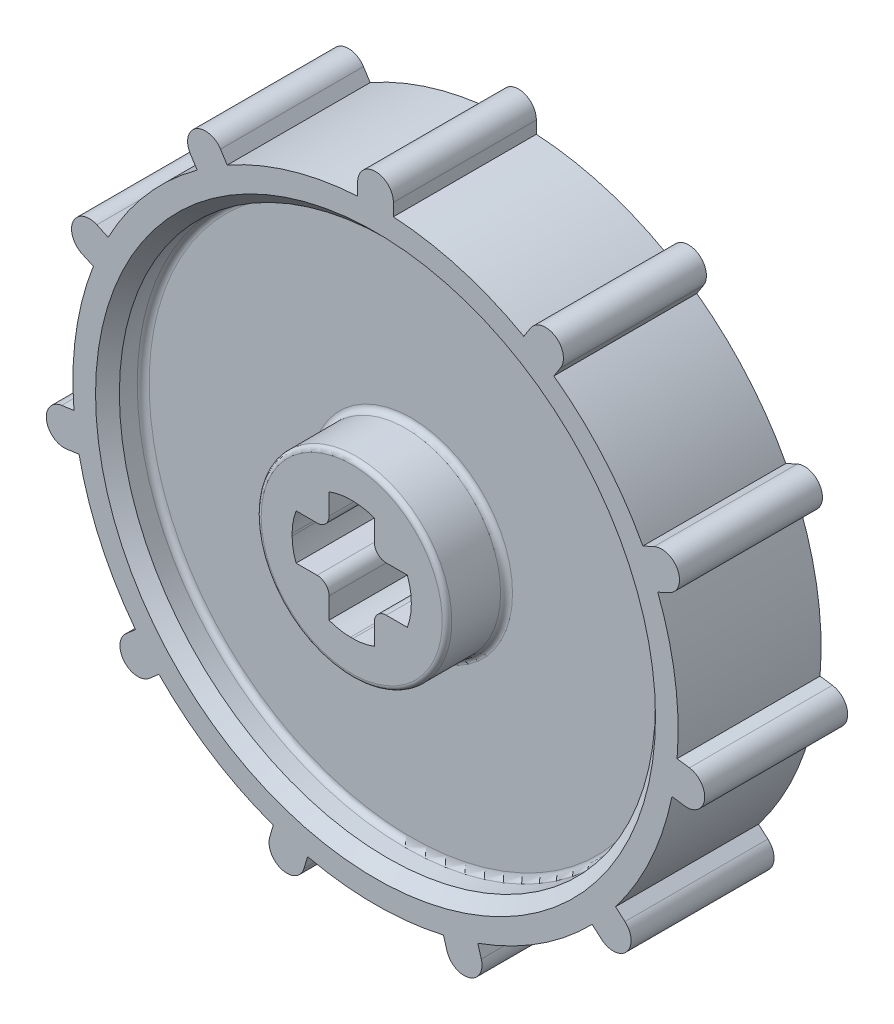
SolidWorks part; units mm, degrees
ref_plane "Front Plane" through (0, 0, 0) normal (0, 0, 1) x (1, 0, 0)
ref_plane "Top Plane" through (0, 0, 0) normal (0, 1, 0) x (1, 0, 0)
ref_plane "Right Plane" through (0, 0, 0) normal (1, 0, 0) x (0, 0, -1)
sketch "Sketch1" plane through (0, 0, 0) normal (1, 0, 0) x (0, 0, -1)
  line L0 (0, 12.7) -> (7, 12.7)
  line L1 (7, 12.7) -> (7, 11.7)
  line L2 (6.5, 0) -> (0, 0)
  line L3 (0, 0) -> (0, 12.7)
  line L5 (-9.434, 0) -> (0, 0) construction
  line L6 (7, 11.7) -> (6.5, 11.7)
  line L7 (6.5, 11.7) -> (6.5, 0)
  dimension "D1" = 12.7
  dimension "D2" = 7
  dimension "D3" = 0.5
  dimension "D4" = 1
revolve "Revolve1" add sketch "Sketch1" angle 360 about L5
sketch "Sketch2" plane through (0, 0, 0) normal (0, 0, 1) x (1, 0, 0)
  line L0 (0, 12.6778) -> (0, 13.2) construction
  line L1 (-0.75, 12.6778) -> (-0.75, 13.2)
  line L2 (0.75, 12.6778) -> (0.75, 13.2)
  circle A0 centre (0, 0) radius 12.7 construction
  arc A1 (-0.75, 12.6778) -> (0.75, 12.6778) centre (0, 12.6778) ccw
  arc A2 (0.75, 13.2) -> (-0.75, 13.2) centre (0, 13.2) ccw
  point P6 (0, 12.9389)
  point P11 (0, 12.7)
  dimension "D1" = 0.75
  dimension "D2" = 0.5
extrude "Boss-Extrude1" add sketch "Sketch2" against normal up to surface (7 mm away) up to face at (12.7, 0, -7)
pattern_circular "CirPattern1" count 11 over 360 about axis through (0, 0, 9.434) along (0, 0, 1) of "Boss-Extrude1" reverse direction yes
sketch "Sketch3" plane through (0, 0, 0) normal (0, 0, 1) x (1, 0, 0)
  line L0 (-0.95, 2.3324) -> (-0.95, 1.45)
  line L1 (-0.95, 0.95) -> (0, 0) construction
  line L2 (0, 0) -> (0, 2.5) construction
  line L3 (-0.05, 2.5) -> (0.05, 2.5)
  line L4 (-2.5, 0.05) -> (-2.5, -0.05)
  line L5 (-2.3324, 0.95) -> (-1.45, 0.95)
  line L6 (2.5, 0.05) -> (2.5, -0.05)
  line L7 (2.3324, 0.95) -> (1.45, 0.95)
  line L8 (0.95, 2.3324) -> (0.95, 1.45)
  line L9 (-2.5, 0) -> (0, 0) construction
  line L10 (-2.3324, -0.95) -> (-1.45, -0.95)
  line L11 (-0.95, -2.3324) -> (-0.95, -1.45)
  line L12 (-0.05, -2.5) -> (0.05, -2.5)
  line L13 (0.95, -2.3324) -> (0.95, -1.45)
  line L14 (2.3324, -0.95) -> (1.45, -0.95)
  arc A0 (-0.05, 2.5) -> (-0.95, 2.3324) centre (-0.05, 0) ccw
  arc A1 (-2.5, 0.05) -> (-2.3324, 0.95) centre (0, 0.05) cw
  arc A2 (2.5, 0.05) -> (2.3324, 0.95) centre (0, 0.05) ccw
  arc A3 (0.05, 2.5) -> (0.95, 2.3324) centre (0.05, 0) cw
  arc A4 (-2.5, -0.05) -> (-2.3324, -0.95) centre (0, -0.05) ccw
  arc A5 (-0.05, -2.5) -> (-0.95, -2.3324) centre (-0.05, 0) cw
  arc A6 (0.05, -2.5) -> (0.95, -2.3324) centre (0.05, 0) ccw
  arc A7 (2.5, -0.05) -> (2.3324, -0.95) centre (0, -0.05) cw
  arc A8 (-1.45, -0.95) -> (-0.95, -1.45) centre (-1.45, -1.45) cw
  arc A9 (0.95, -1.45) -> (1.45, -0.95) centre (1.45, -1.45) cw
  arc A10 (1.45, 0.95) -> (0.95, 1.45) centre (1.45, 1.45) cw
  arc A11 (-0.95, 1.45) -> (-1.45, 0.95) centre (-1.45, 1.45) cw
  point P33 (2.5, 0)
  point P35 (-0.95, -0.95)
  point P38 (0.95, -0.95)
  point P41 (0.95, 0.95)
  dimension "D4" = 2.5
  dimension "D5" = 0.5
  dimension "D1" = 1.9
  dimension "D2" = 0.1
  dimension "D3" = 5
extrude "Cut-Extrude1" cut sketch "Sketch3" against normal blind 5
sketch "Sketch4" plane through (0, 0, 0) normal (0, 0, 1) x (1, 0, 0)
  circle A0 centre (0, 0) radius 4
  circle A1 centre (0, 0) radius 11.25
  dimension "D1" = 8
  dimension "D2" = 22.5
extrude "Cut-Extrude2" cut sketch "Sketch4" against normal blind 2.5
sketch "Sketch5" plane through (0, 0, 0) normal (0, 0, 1) x (1, 0, 0)
  circle A0 centre (0, 0) radius 4.005
  circle A1 centre (0, 0) radius 6
  dimension "D1" = 12
  dimension "D2" = 8.01
extrude "Boss-Extrude2" [suppressed] add sketch "Sketch5" against normal blind 2.49 separate body
sketch "Sketch6" plane through (0, 0, 0) normal (0, 0, 1) x (1, 0, 0)
  line L22 (-6.2232, 11.0708) -> (-6.5055, 11.51)
  line L23 (-7.7674, 10.6991) -> (-7.4851, 10.2598)
  line L24 (-11.2206, 5.9488) -> (-11.6956, 6.1657)
  line L25 (-12.3187, 4.8013) -> (-11.8437, 4.5843)
  line L26 (-12.6555, -1.0619) -> (-13.1724, -1.1362)
  line L27 (-12.9589, -2.6209) -> (-12.4421, -2.5466)
  line L28 (-10.0724, -7.7354) -> (-10.467, -8.0773)
  line L29 (-9.4847, -9.211) -> (-9.0901, -8.869)
  line L30 (-4.2914, -11.953) -> (-4.4385, -12.454)
  line L31 (-2.9993, -12.8766) -> (-2.8521, -12.3756)
  line L32 (2.8521, -12.3756) -> (2.9993, -12.8766)
  line L33 (4.4385, -12.454) -> (4.2914, -11.953)
  line L34 (9.0901, -8.869) -> (9.4847, -9.211)
  line L35 (10.467, -8.0773) -> (10.0724, -7.7354)
  line L36 (12.4421, -2.5466) -> (12.9589, -2.6209)
  line L37 (13.1724, -1.1362) -> (12.6555, -1.0619)
  line L38 (11.8437, 4.5843) -> (12.3187, 4.8013)
  line L39 (11.6956, 6.1657) -> (11.2206, 5.9488)
  line L40 (7.4851, 10.2598) -> (7.7674, 10.6991)
  line L41 (6.5055, 11.51) -> (6.2232, 11.0708)
  line L42 (0.75, 12.6778) -> (0.75, 13.2)
  line L43 (-0.75, 13.2) -> (-0.75, 12.6778)
  line L44 (-6.2232, 11.0708) -> (-6.5055, 11.51)
  line L45 (-7.7674, 10.6991) -> (-7.4851, 10.2598)
  line L46 (-11.2206, 5.9488) -> (-11.6956, 6.1657)
  line L47 (-12.3187, 4.8013) -> (-11.8437, 4.5843)
  line L48 (-12.6555, -1.0619) -> (-13.1724, -1.1362)
  line L49 (-12.9589, -2.6209) -> (-12.4421, -2.5466)
  line L50 (-10.0724, -7.7354) -> (-10.467, -8.0773)
  line L51 (-9.4847, -9.211) -> (-9.0901, -8.869)
  line L52 (-4.2914, -11.953) -> (-4.4385, -12.454)
  line L53 (-2.9993, -12.8766) -> (-2.8521, -12.3756)
  line L54 (2.8521, -12.3756) -> (2.9993, -12.8766)
  line L55 (4.4385, -12.454) -> (4.2914, -11.953)
  line L56 (9.0901, -8.869) -> (9.4847, -9.211)
  line L57 (10.467, -8.0773) -> (10.0724, -7.7354)
  line L58 (12.4421, -2.5466) -> (12.9589, -2.6209)
  line L59 (13.1724, -1.1362) -> (12.6555, -1.0619)
  line L60 (11.8437, 4.5843) -> (12.3187, 4.8013)
  line L61 (11.6956, 6.1657) -> (11.2206, 5.9488)
  line L62 (7.4851, 10.2598) -> (7.7674, 10.6991)
  line L63 (6.5055, 11.51) -> (6.2232, 11.0708)
  line L64 (0.75, 12.6778) -> (0.75, 13.2)
  line L65 (-0.75, 13.2) -> (-0.75, 12.6778)
  circle A0 centre (0, 0) radius 11.25 construction
  circle A1 centre (0, 0) radius 11.25
  arc A22 (-0.75, 12.6778) -> (-6.2232, 11.0708) centre (0, 0) ccw
  arc A23 (-6.5055, 11.51) -> (-7.7674, 10.6991) centre (-7.1365, 11.1045) ccw
  arc A24 (-7.4851, 10.2598) -> (-11.2206, 5.9488) centre (0, 0) ccw
  arc A25 (-11.6956, 6.1657) -> (-12.3187, 4.8013) centre (-12.0071, 5.4835) ccw
  arc A26 (-11.8437, 4.5843) -> (-12.6555, -1.0619) centre (0, 0) ccw
  arc A27 (-13.1724, -1.1362) -> (-12.9589, -2.6209) centre (-13.0656, -1.8786) ccw
  arc A28 (-12.4421, -2.5466) -> (-10.0724, -7.7354) centre (0, 0) ccw
  arc A29 (-10.467, -8.0773) -> (-9.4847, -9.211) centre (-9.9759, -8.6442) ccw
  arc A30 (-9.0901, -8.869) -> (-4.2914, -11.953) centre (0, 0) ccw
  arc A31 (-4.4385, -12.454) -> (-2.9993, -12.8766) centre (-3.7189, -12.6653) ccw
  arc A32 (-2.8521, -12.3756) -> (2.8521, -12.3756) centre (0, 0) ccw
  arc A33 (2.9993, -12.8766) -> (4.4385, -12.454) centre (3.7189, -12.6653) ccw
  arc A34 (4.2914, -11.953) -> (9.0901, -8.869) centre (0, 0) ccw
  arc A35 (9.4847, -9.211) -> (10.467, -8.0773) centre (9.9759, -8.6442) ccw
  arc A36 (10.0724, -7.7354) -> (12.4421, -2.5466) centre (0, 0) ccw
  arc A37 (12.9589, -2.6209) -> (13.1724, -1.1362) centre (13.0656, -1.8786) ccw
  arc A38 (12.6555, -1.0619) -> (11.8437, 4.5843) centre (0, 0) ccw
  arc A39 (12.3187, 4.8013) -> (11.6956, 6.1657) centre (12.0071, 5.4835) ccw
  arc A40 (11.2206, 5.9488) -> (7.4851, 10.2598) centre (0, 0) ccw
  arc A41 (7.7674, 10.6991) -> (6.5055, 11.51) centre (7.1365, 11.1045) ccw
  arc A42 (6.2232, 11.0708) -> (0.75, 12.6778) centre (0, 0) ccw
  arc A43 (0.75, 13.2) -> (-0.75, 13.2) centre (0, 13.2) ccw
  arc A44 (-0.75, 12.6778) -> (-6.2232, 11.0708) centre (0, 0) ccw
  arc A45 (-6.5055, 11.51) -> (-7.7674, 10.6991) centre (-7.1365, 11.1045) ccw
  arc A46 (-7.4851, 10.2598) -> (-11.2206, 5.9488) centre (0, 0) ccw
  arc A47 (-11.6956, 6.1657) -> (-12.3187, 4.8013) centre (-12.0071, 5.4835) ccw
  arc A48 (-11.8437, 4.5843) -> (-12.6555, -1.0619) centre (0, 0) ccw
  arc A49 (-13.1724, -1.1362) -> (-12.9589, -2.6209) centre (-13.0656, -1.8786) ccw
  arc A50 (-12.4421, -2.5466) -> (-10.0724, -7.7354) centre (0, 0) ccw
  arc A51 (-10.467, -8.0773) -> (-9.4847, -9.211) centre (-9.9759, -8.6442) ccw
  arc A52 (-9.0901, -8.869) -> (-4.2914, -11.953) centre (0, 0) ccw
  arc A53 (-4.4385, -12.454) -> (-2.9993, -12.8766) centre (-3.7189, -12.6653) ccw
  arc A54 (-2.8521, -12.3756) -> (2.8521, -12.3756) centre (0, 0) ccw
  arc A55 (2.9993, -12.8766) -> (4.4385, -12.454) centre (3.7189, -12.6653) ccw
  arc A56 (4.2914, -11.953) -> (9.0901, -8.869) centre (0, 0) ccw
  arc A57 (9.4847, -9.211) -> (10.467, -8.0773) centre (9.9759, -8.6442) ccw
  arc A58 (10.0724, -7.7354) -> (12.4421, -2.5466) centre (0, 0) ccw
  arc A59 (12.9589, -2.6209) -> (13.1724, -1.1362) centre (13.0656, -1.8786) ccw
  arc A60 (12.6555, -1.0619) -> (11.8437, 4.5843) centre (0, 0) ccw
  arc A61 (12.3187, 4.8013) -> (11.6956, 6.1657) centre (12.0071, 5.4835) ccw
  arc A62 (11.2206, 5.9488) -> (7.4851, 10.2598) centre (0, 0) ccw
  arc A63 (7.7674, 10.6991) -> (6.5055, 11.51) centre (7.1365, 11.1045) ccw
  arc A64 (6.2232, 11.0708) -> (0.75, 12.6778) centre (0, 0) ccw
  arc A65 (0.75, 13.2) -> (-0.75, 13.2) centre (0, 13.2) ccw
  dimension "D1" = 0
extrude "Cut-Extrude3" cut sketch "Sketch6" against normal blind 1
chamfer "Chamfer1" distance 0.5 angle 45 1 edges at (11.25, 0, -1)
fillet "Fillet1" radius 0.25 2 edges at (11.25, 0, -2.5) (4, 0, -2.5)
fillet "Fillet2" radius 0.2 1 edges at (4, 0, 0)
chamfer "Chamfer2" distance 0.5 angle 75 1 edges at (11.7, 0, -6.5) first distance on face at (11.7, 0, -7)
